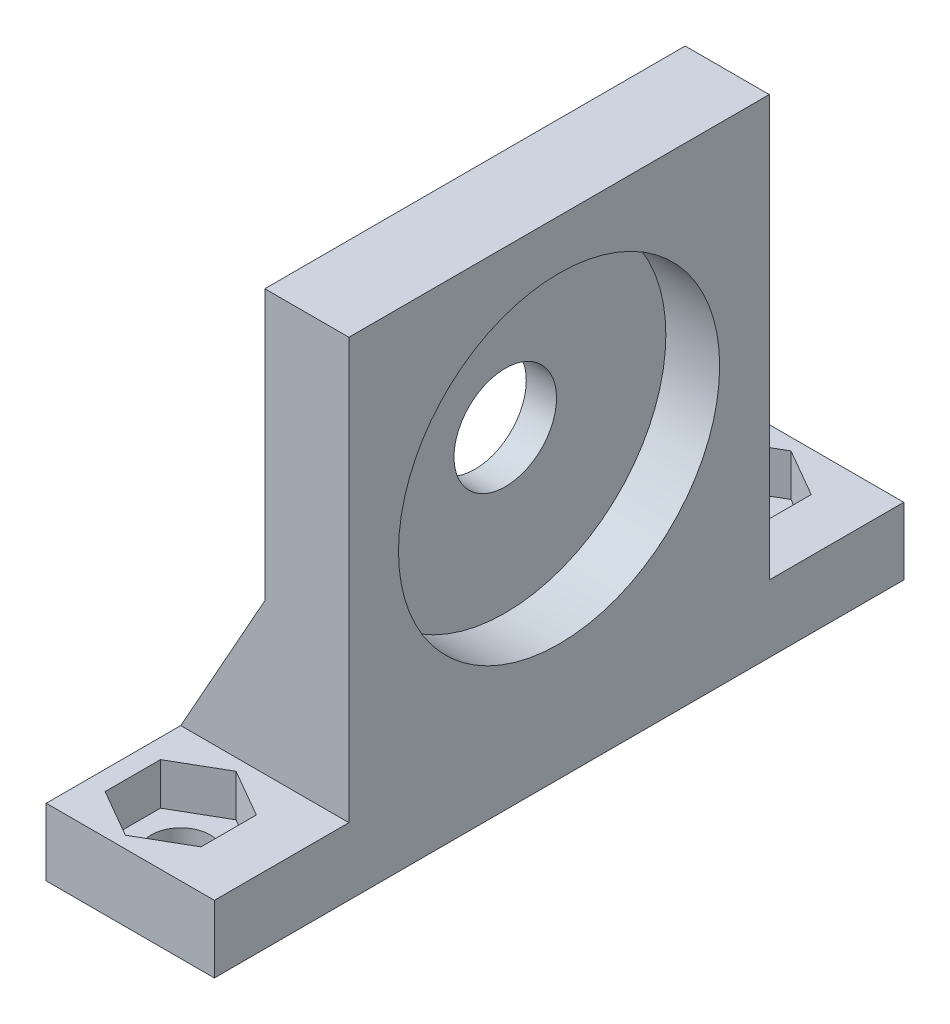
SolidWorks part; units mm, degrees
note: The reader was unsure of these and kept them because the rebuilt part matched: shared geometry of "Sketch1<3>", "Sketch1<4>".
ref_plane "Front Plane" through (0, 0, 0) normal (0, 0, 1) x (1, 0, 0)
ref_plane "Top Plane" through (0, 0, 0) normal (0, 1, 0) x (1, 0, 0)
ref_plane "Right Plane" through (0, 0, 0) normal (1, 0, 0) x (0, 0, -1)
sketch "Sketch1" plane through (0, 0, 0) normal (0, 1, 0) x (1, 0, 0)
  line L0 (0, 0) -> (0, 25)
  line L1 (7, 25) -> (13, 25)
  line L2 (20, 25) -> (20, 0)
  line L3 (13, 0) -> (7, 0)
  line L4 (7, 25) -> (7, 0)
  line L5 (7, 0) -> (13, 0)
  line L6 (13, 0) -> (13, 25)
  line L7 (0, 0) -> (0, -8)
  line L8 (0, -8) -> (20, -8)
  line L9 (20, -8) -> (20, 0)
  line L10 (20, 12.5) -> (1.6032, 12.5) construction
  line L11 (20, 33) -> (20, 25)
  line L12 (0, 33) -> (20, 33)
  line L13 (0, 25) -> (0, 33)
  line L14 (1.15, -2.3546) -> (4, -0.7091)
  line L15 (4, 25.7091) -> (6.85, 27.3546)
  line L16 (6.85, 27.3546) -> (6.85, 30.6454)
  line L17 (6.85, 30.6454) -> (4, 32.2909)
  line L18 (4, 32.2909) -> (1.15, 30.6454)
  line L19 (1.15, 30.6454) -> (1.15, 27.3546)
  line L20 (1.15, 27.3546) -> (4, 25.7091)
  line L21 (1.15, -5.6454) -> (1.15, -2.3546)
  line L22 (4, -7.2909) -> (1.15, -5.6454)
  line L23 (6.85, -5.6454) -> (4, -7.2909)
  line L24 (6.85, -2.3546) -> (6.85, -5.6454)
  line L25 (4, -0.7091) -> (6.85, -2.3546)
  line L26 (10, 33) -> (10, -8) construction
  line L27 (18.85, -5.6454) -> (18.85, -2.3546)
  line L28 (16, -7.2909) -> (18.85, -5.6454)
  line L29 (13.15, -5.6454) -> (16, -7.2909)
  line L30 (13.15, -2.3546) -> (13.15, -5.6454)
  line L31 (16, -0.7091) -> (13.15, -2.3546)
  line L32 (18.85, -2.3546) -> (16, -0.7091)
  line L33 (18.85, 27.3546) -> (16, 25.7091)
  line L34 (18.85, 30.6454) -> (18.85, 27.3546)
  line L35 (16, 32.2909) -> (18.85, 30.6454)
  line L36 (13.15, 30.6454) -> (16, 32.2909)
  line L37 (13.15, 27.3546) -> (13.15, 30.6454)
  line L38 (16, 25.7091) -> (13.15, 27.3546)
  circle A1 centre (4, -4) radius 1.75
  circle A3 centre (16, -4) radius 1.75
  circle A4 centre (16, 29) radius 1.75
  circle A5 centre (4, 29) radius 1.75
  circle A6 centre (4, 29) radius 2.85 construction
  dimension "D2" = 5.7
  dimension "D3" = 6
  dimension "D4" = 20
  dimension "D5" = 7
  dimension "D6" = 4
  dimension "D7" = 4
  dimension "D8" = 4
  dimension "D11" = 20.5
extrude "Boss-Extrude1" add sketch "Sketch1" along normal blind 4 contours L13 L0 L7 L8 L9 L2 L11 L12 L32 L27 L28 L29 L30 L31 L20 L19 L18 L17 L16 L15 L6 L3 L4 L1 L14 L25 L24 L23 L22 L21 L33 L38 L37 L36 L35 L34 | L27 L32 L31 L30 L29 L28 A3 | L38 L33 L34 L35 L36 L37 A4 | L19 L20 L15 L16 L17 L18 A5 | A1
extrude "Boss-Extrude2" add sketch "Sketch1<3>" along normal blind 29 contours L3 L6 L1 L4 | L10 L6 L1 L4
sketch "Sketch1<3>" plane through (0, 0, 0) normal (0, 1, 0) x (1, 0, 0) same geometry as "Sketch1"
sketch "Sketch2" plane through (13, 0, 0) normal (1, 0, 0) x (0, 0, -1)
  line L0 (0, 29) -> (25, 29) construction
  circle A0 centre (12.5, 16.5) radius 9.55
  point P4 (12.5, 29)
  dimension "D1" = 19.1
extrude "Cut-Extrude1" cut sketch "Sketch2" against normal blind 29
sketch "Sketch3" plane through (0, 0, 0) normal (0, 0, 1) x (1, 0, 0)
  line L0 (13, 16.5) -> (20, 4)
  line L1 (13, 29) -> (13, 4) construction
rib "Rib1" sketch "Sketch3" sketch "Sketch3" thickness 2.95 extrusion direction parallel to sketch draft on no parameters "D1"=2.95
sketch "Sketch4" plane through (0, 0, 0) normal (0, 0, 1) x (1, 0, 0)
  line L0 (7, 16.5) -> (0, 4)
  line L1 (7, 29) -> (7, 4) construction
rib "Rib7" sketch "Sketch4" sketch "Sketch4" thickness 2.95 extrusion direction parallel to sketch draft on no parameters "D1"=2.95
ref_plane "Plane1" through (0, 0, -12.5) normal (0, 0, 1) x (1, 0, 0)
mirror "Mirror1" about plane through (0, 0, -12.5) normal (0, 0, 1) of "Rib1", "Rib7"
extrude "Cut-Extrude4" cut sketch "Sketch1<4>" against normal blind 2.5 from surface at 4 contours L25 L14 L21 L22 L23 L24 A1 | L19 L20 L15 L16 L17 L18 A5 | L38 L33 L34 L35 L36 L37 A4 | L27 L32 L31 L30 L29 L28 A3 starting at face at (10, 4, 4)
sketch "Sketch1<4>" plane through (0, 0, 0) normal (0, 1, 0) x (1, 0, 0) same geometry as "Sketch1"
sketch "Sketch5" plane through (7, 0, 0) normal (-1, 0, 0) x (0, 0, 1)
  line L1 (0, 29) -> (-25, 29)
  line L2 (0, 29) -> (0, 4)
  line L3 (0, 4) -> (-25, 4)
  line L4 (-25, 29) -> (-25, 4)
  circle A0 centre (-12.5, 16.5) radius 3.05
  dimension "D1" = 6.1
extrude "Boss-Extrude3" add sketch "Sketch5" along normal blind 2
ref_plane "Plane2" through (10, 0, 0) normal (1, 0, 0) x (0, 0, -1)
other "SurfaceCut1" flip cut yes
sketch "Sketch6" plane through (7, 0, 0) normal (1, 0, 0) x (0, 0, -1)
  circle A0 centre (12.5, 16.5) radius 9.55
extrude "Cut-Extrude5" cut sketch "Sketch6" against normal blind 0.2
